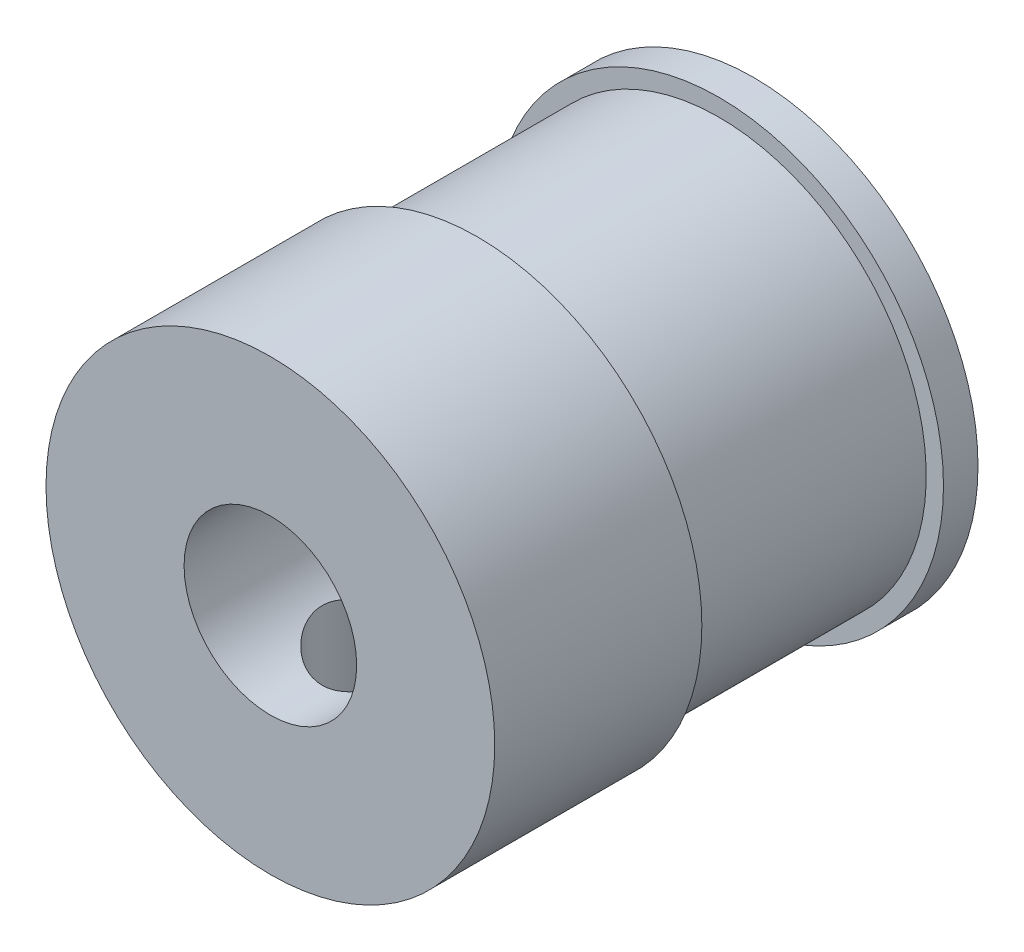
SolidWorks part; units mm, degrees
ref_plane "Front Plane" through (0, 0, 0) normal (0, 0, 1) x (1, 0, 0)
ref_plane "Top Plane" through (0, 0, 0) normal (0, 1, 0) x (1, 0, 0)
ref_plane "Right Plane" through (0, 0, 0) normal (1, 0, 0) x (0, 0, -1)
sketch "Sketch1" plane through (0, 0, 0) normal (0, 0, 1) x (1, 0, 0)
  circle A0 centre (0, 0) radius 6.5
  dimension "D1" = 13
extrude "Boss-Extrude1" add sketch "Sketch1" along normal blind 14
sketch "Sketch2" plane through (0, 0, 14) normal (0, 0, 1) x (1, 0, 0)
  circle A0 centre (0, 0) radius 2.5
  dimension "D1" = 5
extrude "Cut-Extrude1" cut sketch "Sketch2" against normal through all
ref_plane "Plane1" through (0, 0, 1) normal (0, 0, -1) x (-1, 0, 0)
sketch "Sketch3" plane through (0, 0, 1) normal (0, 0, -1) x (-1, 0, 0)
  circle A0 centre (0, 0) radius 6
  circle A1 centre (0, 0) radius 6.5 construction
  circle A2 centre (0, 0) radius 6.5
  dimension "D1" = 0.5
extrude "Cut-Extrude2" cut sketch "Sketch3" against normal blind 7
sketch "Sketch4" plane through (0, 0, 0) normal (0, 1, 0) x (1, 0, 0)
  line L0 (0, -14) -> (0, -11) construction
  line L1 (-6.5, -14) -> (6.5, -14) construction
  circle A0 centre (0, -11) radius 1.5
  dimension "D1" = 3
  dimension "D2" = 3
extrude "Cut-Extrude3" cut sketch "Sketch4" against normal blind 7
